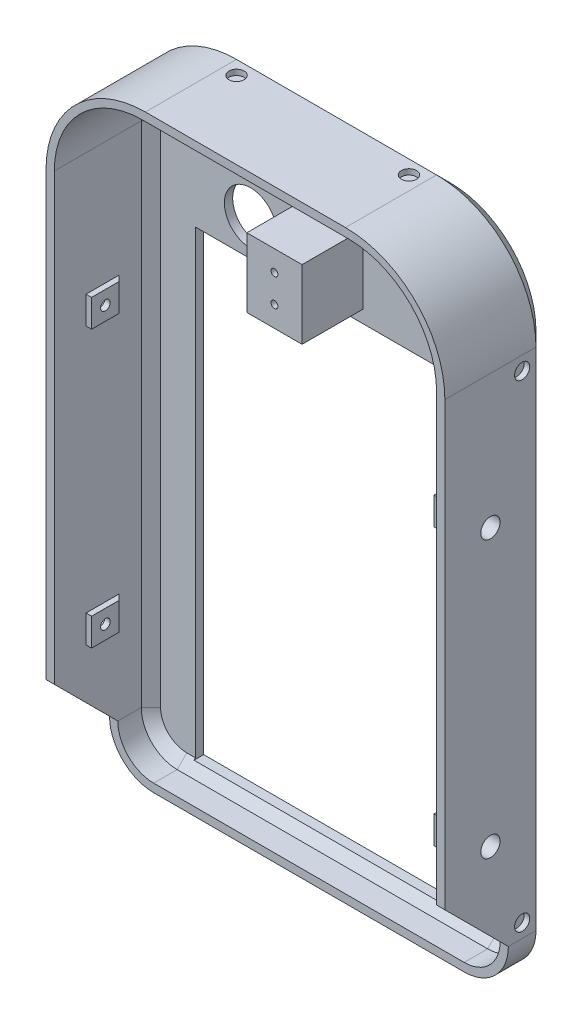
SolidWorks part; units mm, degrees
ref_plane "Plan de face" through (0, 0, 0) normal (0, 0, 1) x (1, 0, 0)
ref_plane "Plan de dessus" through (0, 0, 0) normal (0, 1, 0) x (1, 0, 0)
ref_plane "Plan de droite" through (0, 0, 0) normal (1, 0, 0) x (0, 0, -1)
sketch "Esquisse1" plane through (0, 0, 0) normal (0, 0, 1) x (1, 0, 0)
  line L1 (-12.2348, 13.2576) -> (7.7652, 13.2576)
  line L2 (-12.2348, 13.2576) -> (-12.2348, -11.7424)
  line L3 (-12.2348, -11.7424) -> (7.7652, -11.7424)
  line L4 (7.7652, 13.2576) -> (7.7652, -11.7424)
  dimension "D1" = 20
  dimension "D2" = 25
extrude "Boss.-Extru.1" add sketch "Esquisse1" along normal blind 22
sketch "Esquisse2" plane through (0, 0, 22) normal (0, 0, 1) x (1, 0, 0)
  line L0 (-12.2348, 0.7576) -> (7.7652, 0.7576) construction
  line L1 (-12.2348, 13.2576) -> (-12.2348, -11.7424) construction
  line L2 (7.7652, -11.7424) -> (7.7652, 13.2576) construction
  line L3 (-2.2348, 5.7576) -> (-2.2348, -4.2424) construction
  circle A0 centre (-2.2348, 5.7576) radius 1.25
  circle A1 centre (-2.2348, -4.2424) radius 1.25
  point P13 (-2.2348, 0.7576)
  point P14 (-2.2348, 0.7576)
  dimension "D2" = 2.5
  dimension "D1" = 10
extrude "Enlèv. mat.-Extru.1" cut sketch "Esquisse2" against normal blind 15
sketch "Esquisse3" plane through (0, 0, 0) normal (0, 0, -1) x (-1, 0, 0)
  line L1 (71.9648, -16.2424) -> (-72.4852, -16.2424)
  line L2 (71.9648, -16.2424) -> (71.9648, 45.7576)
  line L3 (71.9648, 45.7576) -> (-72.4852, 45.7576)
  line L4 (-72.4852, -16.2424) -> (-72.4852, 45.7576)
  line L5 (-7.7652, 13.2576) -> (12.2348, 13.2576) construction
  line L7 (12.2348, -11.7424) -> (-7.7652, -11.7424) construction
  line L8 (12.2348, 13.2576) -> (12.2348, -11.7424) construction
  line L9 (-7.7652, -11.7424) -> (-7.7652, 13.2576) construction
  dimension "D1" = 4.5
  dimension "D2" = 59.73
  dimension "D3" = 64.72
  dimension "D4" = 32.5
extrude "Wall" add sketch "Esquisse3" along normal blind 3
sketch "Esquisse4" plane through (0, 0, -3) normal (0, 0, -1) x (-1, 0, 0)
  line L1 (-72.4852, -16.2424) -> (71.9648, -16.2424) construction
  line L2 (12.2348, 13.2576) -> (12.2348, -11.7424) construction
  line L3 (-32.5352, 28.7576) -> (32.4648, 28.7576) construction
  line L4 (-32.5352, 39.2576) -> (32.4648, 39.2576)
  line L5 (-32.5352, 18.2576) -> (32.4648, 18.2576)
  line L7 (71.9648, -16.2424) -> (71.9648, 45.7576) construction
  circle A0 centre (32.8698, -3.4521) radius 9.5
  arc A1 (-32.5352, 39.2576) -> (-32.5352, 18.2576) centre (-32.5352, 28.7576) ccw
  arc A2 (32.4648, 18.2576) -> (32.4648, 39.2576) centre (32.4648, 28.7576) ccw
  point P8 (-0.0352, 28.7576)
  dimension "D1" = 19
  dimension "D7" = 10.5
  dimension "D2" = 20.635
  dimension "D3" = 12.7903
  dimension "D4" = 45
  dimension "D5" = 39.5
  dimension "D6" = 65
extrude "Cameras" cut sketch "Esquisse4" against normal up to next
sketch "Esquisse9" plane through (0, 0, -3) normal (0, 0, -1) x (-1, 0, 0)
  line L0 (-49.1352, -183.2424) -> (52.8648, -183.2424)
  line L1 (-72.4852, -16.2424) -> (-49.1352, -16.2424)
  line L2 (-72.4852, -16.2424) -> (-72.4852, -189.2424)
  line L4 (-49.1352, -16.2424) -> (-49.1352, -183.2424)
  line L5 (71.9648, -16.2424) -> (52.8648, -16.2424)
  line L6 (71.9648, -16.2424) -> (71.9648, -189.2424)
  line L8 (52.8648, -16.2424) -> (52.8648, -183.2424)
  line L9 (-72.4852, -189.2424) -> (71.9648, -189.2424)
  dimension "D1" = 23.35
  dimension "D2" = 19.1
  dimension "D3" = 167
  dimension "D4" = 6
extrude "Screen" add sketch "Esquisse9" against normal up to surface (3 mm away) up to face at (-42.3698, -3.4521, 0)
sketch "Esquisse5" plane through (0, 0, 0) normal (0, 0, 1) x (1, 0, 0)
  line L2 (-71.9648, -189.2424) -> (-71.9648, 45.7576)
  line L7 (72.4852, 45.7576) -> (72.4852, -189.2424)
  line L10 (-71.9648, 45.7576) -> (72.4852, 45.7576) construction
  line L11 (-71.9648, 45.7576) -> (72.4852, 45.7576)
  line L12 (-68.9648, -186.2424) -> (-68.9648, 42.7576)
  line L13 (-68.9648, 42.7576) -> (69.4852, 42.7576)
  line L14 (69.4852, 42.7576) -> (69.4852, -186.2424)
  line L15 (0.2602, 42.7576) -> (0.2602, 45.7576) construction
  line L18 (-71.9648, -189.2424) -> (72.4852, -189.2424) construction
  line L19 (-68.9648, -186.2424) -> (69.4852, -186.2424)
  line L20 (0.2602, -186.2424) -> (0.2602, -189.2424) construction
  line L21 (-68.9648, -186.2424) -> (-71.9648, -186.2424) construction
  line M11 (-71.9648, 45.7576) -> (-71.9648, -189.2424)
  line M13 (72.4852, -189.2424) -> (72.4852, 45.7576)
  line M14 (72.4852, 45.7576) -> (-71.9648, 45.7576)
  line M32 (-71.9648, -189.2424) -> (72.4852, -189.2424)
  dimension "D1" = 3
extrude "Boss.-Extru.3" add sketch "Esquisse5" along normal blind 35 contours L19 L12 L13 L14 M14 M11 M32 M13 region at (-69.2064, -71.7424, 0)
fillet "Congé1" radius 32 2 edges at (-68.9648, 42.7576, 17.5) (69.4852, 42.7576, 17.5)
fillet "Congé2" radius 36 2 edges at (-71.9648, 45.7576, 16) (72.4852, 45.7576, 16)
fillet "Congé3" radius 13 2 edges at (-68.9648, -186.2424, 17.5) (69.4852, -186.2424, 17.5)
fillet "Congé4" radius 16 2 edges at (-71.9648, -189.2424, 16) (72.4852, -189.2424, 16)
chamfer "Chanfrein1" distance 5 angle 45 8 edges at (-71.9648, -81.7424, -3) (-61.4207, 35.2134, -3) (0.2602, 45.7576, -3) (72.4852, -81.7424, -3) (61.941, 35.2134, -3) (-67.2786, -184.5561, -3) (0.2602, -189.2424, -3) (67.7989, -184.5561, -3)
chamfer "Chanfrein2" distance 3.5 angle 45 8 edges at (-68.9648, -81.2424, 0) (-59.5923, 33.385, 0) (69.4852, -81.2424, 0) (0.2602, 42.7576, 0) (60.1126, 33.385, 0) (-65.1572, -182.4348, 0) (0.2602, -186.2424, 0) (65.6775, -182.4348, 0)
sketch "Esquisse16" plane through (72.4852, 0, 0) normal (1, 0, 0) x (0, 0, -1)
  line L0 (-35, -150.2424) -> (-12, -173.2424)
  line L1 (-12, -173.2424) -> (-12, -189.2424)
  line L2 (-12, -189.2424) -> (-35, -189.2424)
  line L3 (-35, -189.2424) -> (-35, -150.2424)
  line L4 (-2, -189.2424) -> (-2, -173.2424) construction
  line L5 (-35, -189.2424) -> (-2, -189.2424) construction
  line L8 (-35, -173.2424) -> (-35, 9.7576) construction
  line L9 (-35, -173.2424) -> (-2, -173.2424) construction
  dimension "D1" = 10
  dimension "D2" = 45
extrude "Enlèv. mat.-Extru.9" cut sketch "Esquisse16" against normal through all
ref_plane "Plan1" through (0, 0, 13.5) normal (0, 0, 1) x (1, 0, 0)
sketch "Esquisse11" plane through (0, 0, 13.5) normal (0, 0, 1) x (1, 0, 0)
  line L1 (69.4852, -143.6314) -> (57.0352, -143.6314)
  line L3 (69.4852, -33.6314) -> (57.0352, -33.6314)
  line L5 (-66.9648, -143.6314) -> (-68.9648, -143.6314)
  line L7 (-66.9648, -33.6314) -> (-68.9648, -33.6314)
  line L9 (57.0352, -33.6314) -> (57.0352, -43.6314)
  line L10 (49.1352, -16.2424) -> (-52.8648, -16.2424) construction
  line L11 (57.0352, -43.6314) -> (69.4852, -43.6314)
  line L12 (69.4852, -43.6314) -> (69.4852, -33.6314)
  line L13 (69.4852, -173.2424) -> (69.4852, -150.2424) construction
  line L14 (57.0352, -143.6314) -> (57.0352, -133.6314)
  line L15 (57.0352, -133.6314) -> (69.4852, -133.6314)
  line L16 (69.4852, -133.6314) -> (69.4852, -143.6314)
  line L17 (-66.9648, -33.6314) -> (-66.9648, -43.6314)
  line L18 (-66.9648, -43.6314) -> (-68.9648, -43.6314)
  line L19 (-68.9648, -43.6314) -> (-68.9648, -33.6314)
  line L20 (-66.9648, -143.6314) -> (-66.9648, -133.6314)
  line L21 (-66.9648, -133.6314) -> (-68.9648, -133.6314)
  line L22 (-68.9648, -133.6314) -> (-68.9648, -143.6314)
  line L23 (-68.9648, -150.2424) -> (-68.9648, 10.7576) construction
  point P21 (57.0352, -138.6314)
  point P22 (57.0352, -38.6314)
  dimension "D1" = 12.45
  dimension "D2" = 2
  dimension "D3" = 10
  dimension "D4" = 100
  dimension "D5" = 22.3889
extrude "Boss.-Extru.5" add sketch "Esquisse11" along normal blind 10
chamfer "Chanfrein3" distance 2 angle 45 2 edges at (-68.9648, -38.6314, 13.5) (-68.9648, -138.6314, 13.5)
chamfer "Chanfrein4" distance 12.45 angle 45 2 edges at (69.4852, -38.6314, 13.5) (69.4852, -138.6314, 13.5)
sketch "Esquisse12" plane through (57.0352, 0, 0) normal (-1, 0, 0) x (0, 0, 1)
  line L1 (23.5, -33.6314) -> (23.5, -43.6314) construction
  line L3 (23.5, -33.6314) -> (13.5, -33.6314) construction
  circle A0 centre (18.5, -38.6314) radius 1.75
  circle A1 centre (18.5, -138.6314) radius 1.75
  point P10 (23.5, -38.6314)
  point P12 (18.5, -33.6314)
  dimension "D2" = 3.5
  dimension "D3" = 100
extrude "Enlèv. mat.-Extru.5" cut sketch "Esquisse12" against normal through all both and the other way through all
sketch "Esquisse13" plane through (-71.9648, 0, 0) normal (-1, 0, 0) x (0, 0, 1)
  circle A0 centre (18.5, -38.6314) radius 3.5
  circle A1 centre (18.5, -138.6314) radius 3.5
  dimension "D1" = 7
extrude "Enlèv. mat.-Extru.6" cut sketch "Esquisse13" against normal blind 3
sketch "Esquisse14" plane through (72.4852, 0, 0) normal (1, 0, 0) x (0, 0, -1)
  circle A2 centre (-18.5, -138.6314) radius 3.5 construction
  circle A3 centre (-18.5, -38.6314) radius 3.5 construction
  circle A4 centre (-18.5, -138.6314) radius 3.5
  circle A5 centre (-18.5, -38.6314) radius 3.5
extrude "Enlèv. mat.-Extru.7" cut sketch "Esquisse14" against normal offset from surface (13.45 mm away) 2 up to face at (57.0352, -38.6314, 16.75)
sketch "Esquisse6" plane through (0, 45.7576, 0) normal (0, 1, 0) x (1, 0, 0)
  line L1 (36.4852, -35) -> (36.4852, -2) construction
  line L2 (31.4852, -7) -> (36.4852, -7) construction
  line L4 (-30.9648, -7) -> (-35.9648, -7) construction
  line L5 (-35.9648, -2) -> (-35.9648, -35) construction
  line L7 (36.4852, -2) -> (-35.9648, -2) construction
  circle A0 centre (31.4852, -7) radius 2.75
  circle A1 centre (-30.9648, -7) radius 2.75
  dimension "D2" = 5.5
  dimension "D1" = 5
  dimension "D3" = 5
extrude "Enlèv. mat.-Extru.2" cut sketch "Esquisse6" against normal blind 2
sketch "Esquisse7" plane through (72.4852, 0, 0) normal (1, 0, 0) x (0, 0, -1)
  line L0 (-2, 9.7576) -> (-35, 9.7576) construction
  line L2 (-2, -173.2424) -> (-2, 9.7576) construction
  line L3 (-7, -168.2424) -> (-7, -173.2424) construction
  line L5 (-7, 4.7576) -> (-7, 9.7576) construction
  line L6 (-2, 9.7576) -> (-35, 9.7576) construction
  line L7 (-12, -173.2424) -> (-2, -173.2424) construction
  circle A0 centre (-7, 4.7576) radius 2.75
  circle A1 centre (-7, -168.2424) radius 2.75
  dimension "D1" = 5.5
  dimension "D2" = 5
  dimension "D3" = 5
extrude "Enlèv. mat.-Extru.3" cut sketch "Esquisse7" against normal blind 2
sketch "Esquisse8" plane through (-71.9648, 0, 0) normal (-1, 0, 0) x (0, 0, 1)
  circle A2 centre (7, 4.7576) radius 2.75 construction
  circle A3 centre (7, -168.2424) radius 2.75 construction
  circle A4 centre (7, 4.7576) radius 2.75
  circle A5 centre (7, -168.2424) radius 2.75
extrude "Enlèv. mat.-Extru.4" cut sketch "Esquisse8" against normal blind 2
sketch "Esquisse15" plane through (0, -189.2424, 0) normal (0, -1, 0) x (1, 0, 0)
  circle A0 centre (-30.9648, 7) radius 2.75 construction
  circle A1 centre (31.4852, 7) radius 2.75 construction
  circle A2 centre (-30.9648, 7) radius 2.75
  circle A3 centre (31.4852, 7) radius 2.75
extrude "Enlèv. mat.-Extru.8" cut sketch "Esquisse15" against normal blind 2
